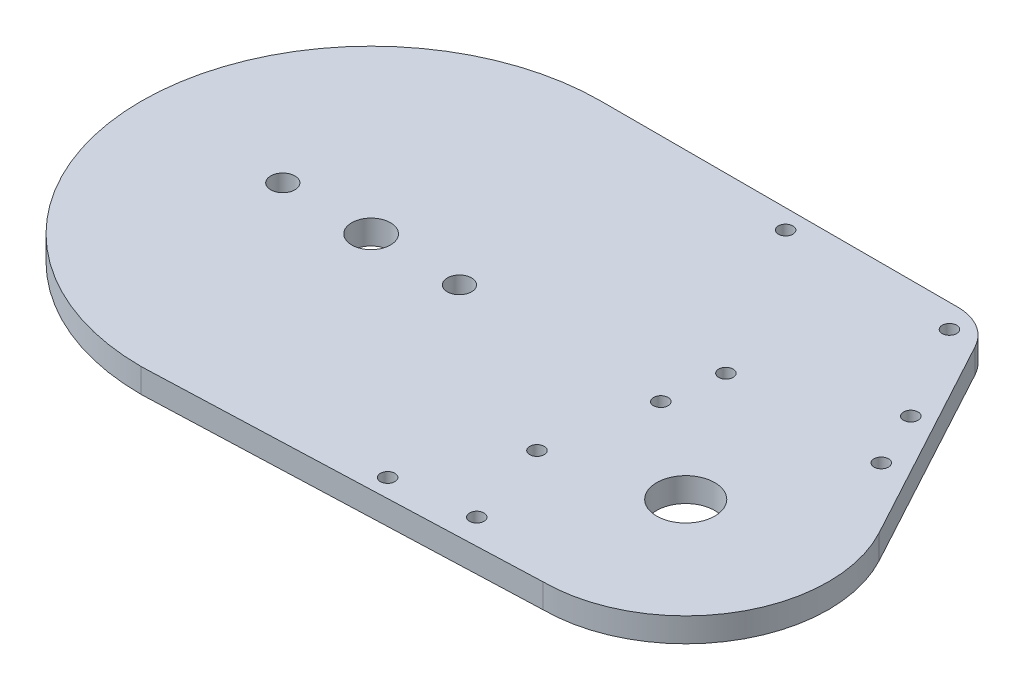
SolidWorks part; units mm, degrees
ref_plane "前视基准面" through (0, 0, 0) normal (0, 0, 1) x (1, 0, 0)
ref_plane "上视基准面" through (0, 0, 0) normal (0, 1, 0) x (1, 0, 0)
ref_plane "右视基准面" through (0, 0, 0) normal (1, 0, 0) x (0, 0, -1)
sketch "Sketch1" plane through (0, 0, 0) normal (0, 1, 0) x (1, 0, 0)
  line L0 (0, 0) -> (0, -15) construction
  line L1 (0, -15) -> (80, -15) construction
  line L2 (0, -47.5) -> (0, -44.5) construction
  line L3 (0, -44.5) -> (94.3585, -44.5) construction
  line L4 (0, -47.5) -> (80, -44.5)
  line L5 (0, 47.5) -> (73.764, 47.5)
  line L6 (82.559, 42.259) -> (105.9453, -0.9611)
  line L7 (0, 0) -> (80, -15) construction
  line L8 (80, -15) -> (59.9347, -0.0875) construction
  line L9 (78.1615, 44.8795) -> (78.8831, 46.0904) construction
  line L10 (78.8831, 46.0904) -> (76.8355, 42.6542) construction
  line L11 (73.764, 47.5) -> (82.559, 42.259) construction
  line L12 (78.1615, 44.8795) -> (73.764, 37.5) construction
  arc A0 (0, 47.5) -> (0, -47.5) centre (0, 0) ccw
  arc A2 (80, -44.5) -> (105.9453, -0.9611) centre (80, -15) ccw
  circle A3 centre (75.0001, 47.5) radius 7.5 construction
  arc A4 (82.559, 42.259) -> (73.764, 47.5) centre (73.764, 37.5) ccw
  circle A5 centre (0, 0) radius 4
  circle A12 centre (80, -15) radius 25 construction
  circle A15 centre (59.9347, -0.0875) radius 1.5
  circle A17 centre (0, 0) radius 18.25 construction
  circle A18 centre (18.25, 0) radius 2.5
  circle A19 centre (-18.25, 0) radius 2.5
  circle A20 centre (80, -15) radius 6
  circle A21 centre (76.8355, 42.6542) radius 1.5
  circle A22 centre (88.3547, 23.1429) radius 1.5
  circle A23 centre (42.1373, 43.5) radius 1.5
  circle A24 centre (45.2934, -41.8851) radius 1.5
  circle A25 centre (61.5917, 11.711) radius 1.5
  circle A26 centre (93.688, 11.711) radius 1.5
  circle A27 centre (61.5917, -39.7686) radius 1.5
  circle A29 centre (55.8953, -21.6306) radius 1.5
  point P28 (75, -15)
  dimension "D1" = 95
  dimension "D4" = 26
  dimension "D6" = 15
  dimension "D7" = 10
  dimension "D8" = 8
  dimension "D9" = 50
  dimension "D10" = 3
  dimension "D12" = 4
  dimension "D11" = 36.5
  dimension "D13" = 5
  dimension "D14" = 5
  dimension "D15" = 12
  dimension "D16" = 3
  dimension "D17" = 3
  dimension "D18" = 3
  dimension "D19" = 3
  dimension "D20" = 3
  dimension "D21" = 3
  dimension "D22" = 3
  dimension "D2" = 15
  dimension "D3" = 80
  dimension "D5" = 3
extrude "Boss-Extrude1" add sketch "Sketch1" along normal blind 5
